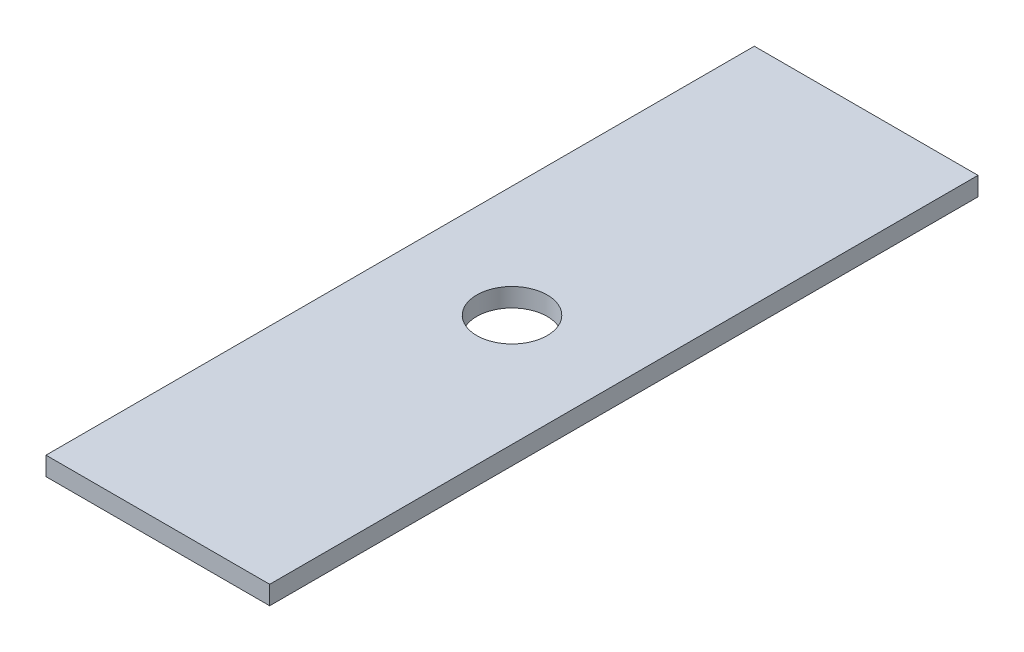
SolidWorks part; units mm, degrees
ref_plane "Front Plane" through (0, 0, 0) normal (0, 0, 1) x (1, 0, 0)
ref_plane "Top Plane" through (0, 0, 0) normal (0, 1, 0) x (1, 0, 0)
ref_plane "Right Plane" through (0, 0, 0) normal (1, 0, 0) x (0, 0, -1)
sketch "Sketch1" plane through (0, 0, 0) normal (0, 0, 1) x (1, 0, 0)
  line L0 (0, 1.5875) -> (0, -1.5875)
  line L1 (-19.05, 0) -> (19.05, 0) construction
  point P6 (0, 0)
  dimension "Width" = 38.1
  dimension "Thk" = 3.175
sketch "Sketch2" plane through (0, 0, 0) normal (1, 0, 0) x (0, 0, -1)
  line L0 (60.325, 0) -> (-60.325, 0)
  point P4 (0, 0)
  dimension "Length" = 120.65
sketch "Sketch3" plane through (0, 0, 0) normal (0, 0, 1) x (1, 0, 0)
  line L1 (19.05, 1.5875) -> (-19.05, 1.5875)
  line L2 (19.05, 1.5875) -> (19.05, -1.5875)
  line L3 (19.05, -1.5875) -> (-19.05, -1.5875)
  line L4 (-19.05, 1.5875) -> (-19.05, -1.5875)
  line L5 (19.05, 1.5875) -> (-19.05, -1.5875) construction
  line L6 (19.05, -1.5875) -> (-19.05, 1.5875) construction
  point P0 (0, 0)
extrude "Boss-Extrude1" add sketch "Sketch3" along normal up to vertex (60.325 mm away) and the other way up to vertex (60.325 mm away) up to point (0, 0, 60.325) other way up to point (0, 0, -60.325)
sketch "Sketch4" plane through (0, 1.5875, 0) normal (0, 1, 0) x (1, 0, 0)
  point P0 (0, 0)
hole_wizard "Ø12.0mm Dowel Hole1" positions "Sketch5" profile "Sketch7" hole size "Ø12.0" standard "ANSI Metric"
sketch "Sketch5" plane through (0, 1.5875, 0) normal (0, 1, 0) x (1, 0, 0)
  point P0 (0, 0)
sketch "Sketch7" plane through (0, 1.5875, 0) normal (1, 0, 0) x (0, 0, 1)
  line L0 (0, 0) -> (0, 13.2572)
  line L1 (0, 13.2572) -> (6, 9.652)
  line L2 (6, 9.652) -> (6, 0)
  line L5 (6, 0) -> (0, 0)
  line L10 (0, 13.2572) -> (-6, 9.652) construction
  line L11 (0, -6.35) -> (0, 107.95) construction
  dimension "Hole Dia." = 12
  dimension "Hole Depth" = 9.652
  dimension "Drill Angle" = 118
